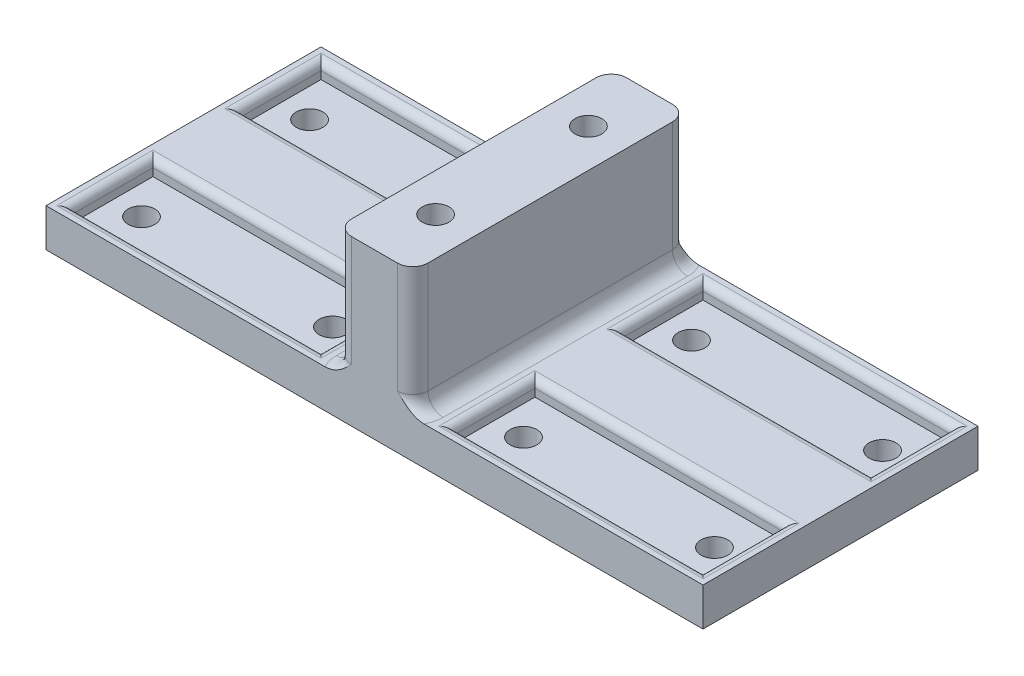
SolidWorks part; units mm, degrees
ref_plane "正面" through (0, 0, 0) normal (0, 0, 1) x (1, 0, 0)
ref_plane "平面" through (0, 0, 0) normal (0, 1, 0) x (1, 0, 0)
ref_plane "右側面" through (0, 0, 0) normal (1, 0, 0) x (0, 0, -1)
sketch "ｽｹｯﾁ1" plane through (0, 0, 0) normal (0, 1, 0) x (1, 0, 0)
  line L1 (-43, 18) -> (43, 18)
  line L2 (-43, 18) -> (-43, -18)
  line L3 (-43, -18) -> (43, -18)
  line L4 (43, 18) -> (43, -18)
  line L5 (-43, 18) -> (43, -18) construction
  line L6 (-43, -18) -> (43, 18) construction
  point P0 (0, 0)
  dimension "D1" = 36
  dimension "D2" = 86
extrude "ﾎﾞｽ - 押し出し1" add sketch "ｽｹｯﾁ1" along normal blind 5
sketch "ｽｹｯﾁ5" plane through (0, 5, 0) normal (0, 1, 0) x (1, 0, 0)
  line L1 (-8.7, -16.3) -> (-41.3, -16.3)
  line L2 (-8.7, -16.3) -> (-8.7, -5.7)
  line L3 (-8.7, -5.7) -> (-41.3, -5.7)
  line L4 (-41.3, -16.3) -> (-41.3, -5.7)
  line L5 (-8.7, -11) -> (-41.3, -11) construction
  line L6 (-25, -16.3) -> (-25, -5.7) construction
  line L7 (43, 0) -> (0, 0) construction
  line L8 (43, -18) -> (43, 18) construction
  line L9 (0, 0) -> (-70.4783, 0) construction
  line L10 (0, 0) -> (0, 18) construction
  line L11 (43, 18) -> (-43, 18) construction
  line L12 (-25, 16.3) -> (-25, 5.7) construction
  line L13 (-8.7, 11) -> (-41.3, 11) construction
  line L14 (-41.3, 16.3) -> (-41.3, 5.7)
  line L15 (-8.7, 5.7) -> (-41.3, 5.7)
  line L16 (-8.7, 16.3) -> (-8.7, 5.7)
  line L17 (-8.7, 16.3) -> (-41.3, 16.3)
  line L18 (8.7, 11) -> (41.3, 11) construction
  line L19 (25, 16.3) -> (25, 5.7) construction
  line L20 (25, -16.3) -> (25, -5.7) construction
  line L21 (8.7, -11) -> (41.3, -11) construction
  line L22 (8.7, 16.3) -> (41.3, 16.3)
  line L23 (8.7, 16.3) -> (8.7, 5.7)
  line L24 (8.7, 5.7) -> (41.3, 5.7)
  line L25 (41.3, 16.3) -> (41.3, 5.7)
  line L26 (41.3, -16.3) -> (41.3, -5.7)
  line L27 (8.7, -5.7) -> (41.3, -5.7)
  line L28 (8.7, -16.3) -> (8.7, -5.7)
  line L29 (8.7, -16.3) -> (41.3, -16.3)
  circle A0 centre (-37.5, -11) radius 1.75
  circle A1 centre (-12.5, -11) radius 1.75
  circle A2 centre (-12.5, 11) radius 1.75
  circle A3 centre (-37.5, 11) radius 1.75
  circle A4 centre (37.5, 11) radius 1.75
  circle A5 centre (12.5, 11) radius 1.75
  circle A6 centre (12.5, -11) radius 1.75
  circle A7 centre (37.5, -11) radius 1.75
  dimension "D5" = 3.5
  dimension "D7" = 3.8
  dimension "D1" = 10.6
  dimension "D2" = 32.6
  dimension "D3" = 11
  dimension "D4" = 12.5
  dimension "D6" = 0
extrude "ｶｯﾄ - 押し出し2" cut sketch "ｽｹｯﾁ5" against normal blind 2
extrude "ｶｯﾄ - 押し出し3" cut sketch "ｽｹｯﾁ5<3>" against normal through all contours A7 | A6 | A4 | A5 | A2 | A1 | A0 | A3 region at (-37.5, 5, 11) region at (-12.5, 5, 11) region at (-12.5, 5, -11) region at (37.5, 5, -11) region at (12.5, 5, -11) region at (12.5, 5, 11) region at (37.5, 5, 11)
sketch "ｽｹｯﾁ5<3>" plane through (0, 5, 0) normal (0, 1, 0) x (1, 0, 0) same geometry as "ｽｹｯﾁ5"
fillet "ﾌｨﾚｯﾄ2" radius 1 16 edges at (8.7, 5, -11) (25, 5, -16.3) (25, 5, -5.7) (41.3, 5, -11) (41.3, 5, 11) (25, 5, 16.3) (8.7, 5, 11) (25, 5, 5.7) (-41.3, 5, -11) (-25, 5, -16.3) (-25, 5, -5.7) (-8.7, 5, -11) (-41.3, 5, 11) (-25, 5, 5.7) (-8.7, 5, 11) (-25, 5, 16.3)
sketch "ｽｹｯﾁ8" plane through (0, 5, 0) normal (0, 1, 0) x (1, 0, 0)
  line L0 (-43, -18) -> (43, -18) construction
  line L1 (5, 18) -> (-5, 18)
  line L2 (5, 18) -> (5, -18)
  line L3 (5, -18) -> (-5, -18)
  line L4 (-5, 18) -> (-5, -18)
  line L5 (5, 18) -> (-5, -18) construction
  line L6 (5, -18) -> (-5, 18) construction
  point P0 (0, 0)
  dimension "D1" = 10
extrude "ﾎﾞｽ - 押し出し2" add sketch "ｽｹｯﾁ8" along normal blind 16.5
sketch "ｽｹｯﾁ9" plane through (0, 21.5, 0) normal (0, 1, 0) x (1, 0, 0)
  line L0 (5, 18) -> (-5, 18) construction
  line L1 (-5, 0) -> (5, 0)
  line L2 (5, -18) -> (5, 18) construction
  circle A0 centre (0, -10) radius 1.75
  circle A1 centre (0, 10) radius 1.75
  point P4 (0, 18)
  point P13 (0, 0)
  dimension "D3" = 3.5
  dimension "D4" = 3.5
  dimension "D1" = 20
  dimension "D2" = 10
extrude "ｶｯﾄ - 押し出し4" cut sketch "ｽｹｯﾁ9" against normal through all contours A0 | A1 region at (0, 21.5, 10) region at (0, 21.5, -10)
fillet "ﾌｨﾚｯﾄ3" radius 2 4 edges at (5, 13.25, 18) (-5, 13.25, 18) (-5, 13.25, -18) (5, 13.25, -18)
fillet "ﾌｨﾚｯﾄ4" radius 2 6 edges at (-4.4142, 5, -17.4142) (-4.4142, 5, 17.4142) (4.4142, 5, 17.4142) (4.4142, 5, -17.4142) (-5, 5, 0) (5, 5, 0)
sketch "ｽｹｯﾁ10" plane through (0, 0, 0) normal (0, -1, 0) x (-1, 0, 0)
  circle A0 centre (0, -10) radius 4
  circle A1 centre (0, 10) radius 4
  dimension "D1" = 8
  dimension "D2" = 8
extrude "ｶｯﾄ - 押し出し5" cut sketch "ｽｹｯﾁ10" against normal blind 4
